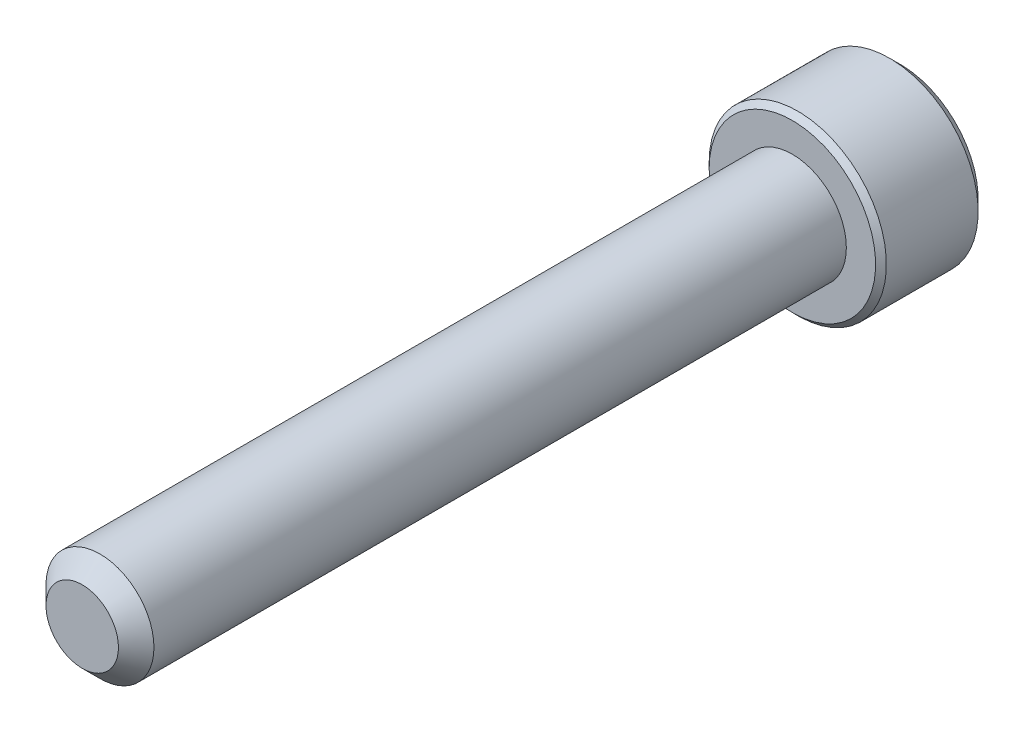
SolidWorks part; units mm, degrees
ref_plane "Front Plane" through (0, 0, 0) normal (0, 0, 1) x (1, 0, 0)
ref_plane "Top Plane" through (0, 0, 0) normal (0, 1, 0) x (1, 0, 0)
ref_plane "Right Plane" through (0, 0, 0) normal (1, 0, 0) x (0, 0, -1)
sketch "Sketch1" plane through (0, 0, 0) normal (0, 0, 1) x (1, 0, 0)
  line L0 (0, 2.413) -> (0, -2.413) construction
  circle A0 centre (0, 0) radius 2.413
  dimension "OD" = 4.826
extrude "Extrude1" add sketch "Sketch1" against normal blind 31.75
sketch "Sketch2" plane through (0, 0, 0) normal (0, 0, 1) x (1, 0, 0)
  circle A0 centre (0, 0) radius 2.413 construction
  circle A1 centre (0, 0) radius 2.413
curve "Helix/Spiral1" pitch 1.0583 height 24.3417 turns 23 parameters "pitch"=1.0583
chamfer "Chamfer3" distance 0.7937 angle 45 1 edges at (2.413, 0, 0)
sketch "Sketch3" plane through (0, 0, 0) normal (1, 0, 0) x (0, 0, -1)
  line L0 (-0.926, 2.413) -> (-0.5292, 1.7256)
  line L1 (-0.5292, 1.7256) -> (-0.3969, 1.7256)
  line L2 (-0.3969, 1.7256) -> (0, 2.413)
  line L3 (-0.926, 2.413) -> (0, 2.413)
  line L4 (-0.463, 2.413) -> (-0.463, 1.7256) construction
  line L5 (-0.7276, 2.0693) -> (-0.1984, 2.0693) construction
  line L6 (0, 2.413) -> (0, -2.413) construction
  dimension "D1" = 0.1323
  dimension "D2" = 0.5292
  dimension "D3" = 60
sweep "Cut-Sweep1" [suppressed] cut profiles "Sketch3" path "Helix/Spiral1"
sketch "Sketch5" plane through (0, 0, 0) normal (1, 0, 0) x (0, 0, -1)
  line L1 (31.75, 2.413) -> (22.225, 2.413)
  line L2 (31.75, 2.413) -> (31.75, 0)
  line L3 (31.75, 0) -> (22.225, 0)
  line L4 (22.225, 2.413) -> (22.225, 0) construction
  line L6 (0, 0) -> (9.9695, 0) construction
  line L8 (22.225, 2.413) -> (19.812, 0)
  line L9 (19.812, 0) -> (22.225, 0)
  line L10 (31.75, -2.413) -> (31.75, 2.413) construction
  dimension "Thread min" = 22.225
  dimension "D1" = 45
revolve "partially thread" add sketch "Sketch5" angle 360 about L6
sketch "Sketch6" plane through (0, 0, -31.75) normal (0, 0, -1) x (-1, 0, 0)
  circle A0 centre (0, 0) radius 3.9624
  dimension "head dia" = 7.9248
extrude "Extrude2" add sketch "Sketch6" along normal blind 4.826
sketch "Sketch7" plane through (0, 0, -36.576) normal (0, 0, -1) x (-1, 0, 0)
  line L1 (0, 2.2914) -> (-1.9844, 1.1457)
  line L2 (-1.9844, 1.1457) -> (-1.9844, -1.1457)
  line L3 (-1.9844, -1.1457) -> (0, -2.2914)
  line L4 (0, -2.2914) -> (1.9844, -1.1457)
  line L5 (1.9844, -1.1457) -> (1.9844, 1.1457)
  line L6 (1.9844, 1.1457) -> (0, 2.2914)
  circle A0 centre (0, 0) radius 1.9844 construction
  dimension "hex dia" = 3.9688
extrude "Cut-Extrude1" cut sketch "Sketch7" against normal blind 2.9766
sketch "Sketch8" plane through (0, 0, -36.576) normal (0, 0, -1) x (-1, 0, 0)
  circle A0 centre (0, 0) radius 2.2914
extrude "Cut-Extrude2" cut sketch "Sketch8" against normal blind 0.4826 draft 45
chamfer "Chamfer1" distance 0.4826 angle 45 1 edges at (-3.9624, 0, -36.576)
chamfer "Chamfer2" distance 0.2413 angle 45 1 edges at (-3.9624, 0, -31.75)
sketch "Sketch9" plane through (0, 0, 0) normal (1, 0, 0) x (0, 0, -1)
  line L0 (0, 2.413) -> (0, -2.413) construction
  line L1 (5.8208, 2.413) -> (5.8208, -2.413) construction
  line L2 (31.75, 3.9624) -> (31.75, -3.9624) construction
  line L3 (36.576, 3.9624) -> (36.576, -3.9624) construction
  line L4 (36.576, 0) -> (0, 0) construction
  line L5 (61.6852, 2.413) -> (61.6852, -2.413) construction
  dimension "D1" = 5.8208
  dimension "D2" = 4.826
  dimension "D3" = 7.9248
  dimension "D4" = 31.75
  dimension "Thread Length" = 61.6852
equation "\"D3@Helix/Spiral1\" = \"Thread min@Sketch5\"+(\"pitch@Helix/Spiral1\"*2)"
equation "\"D1@Sketch3\" = \"pitch@Helix/Spiral1\"*.125"
equation "\"D2@Sketch3\" = \"pitch@Helix/Spiral1\"*.5"
equation "\"D1@Cut-Extrude1\" = \"hex dia@Sketch7\"*.75"
equation "\"D1@Chamfer1\" = \"head depth@Extrude2\"/10"
equation "\"D1@Sketch9\" = \"pitch@Helix/Spiral1\"*5.5"
equation "\"D1@Chamfer2\" = \"D1@Chamfer1\"/2"
equation "\"D1@Cut-Extrude2\" = \"D1@Chamfer2\"*2"
equation "\"D1@Chamfer3\" = \"pitch@Helix/Spiral1\"*.750"
equation "\"D2@Sketch9\" = \"head depth@Extrude2\""
equation "\"D3@Sketch9\" = \"head dia@Sketch6\""
equation "\"D4@Sketch9\" = \"screw length@Extrude1\""
